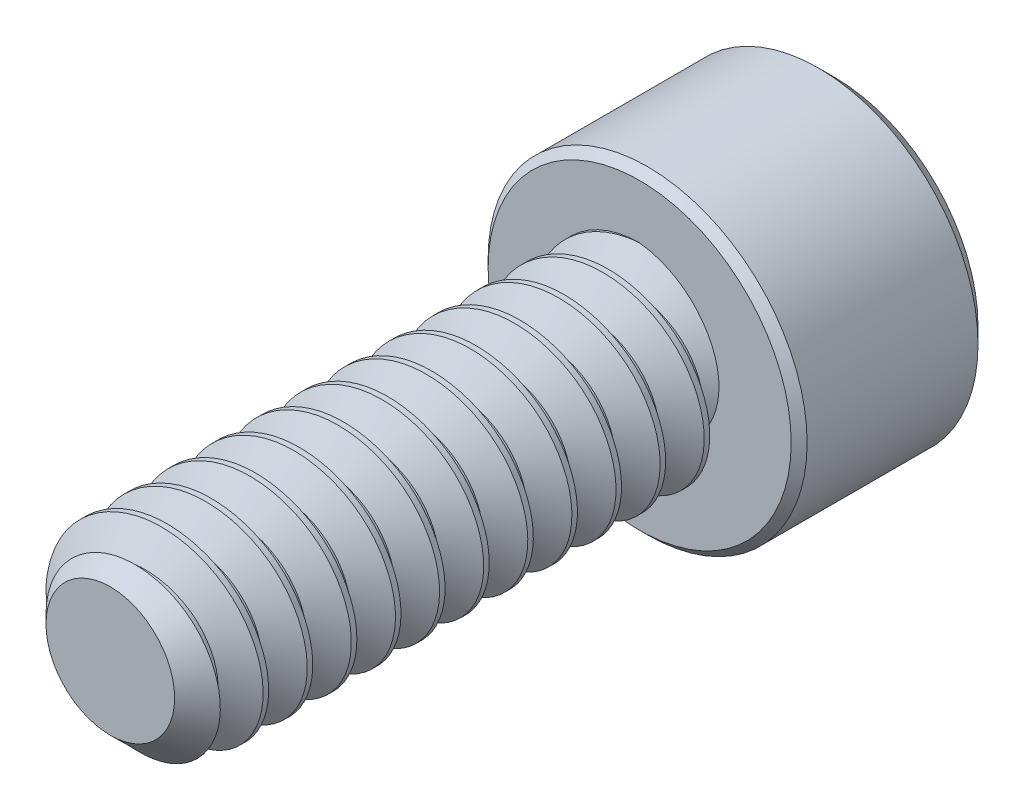
SolidWorks part; units mm, degrees
ref_plane "Front Plane" through (0, 0, 0) normal (0, 0, 1) x (1, 0, 0)
ref_plane "Top Plane" through (0, 0, 0) normal (0, 1, 0) x (1, 0, 0)
ref_plane "Right Plane" through (0, 0, 0) normal (1, 0, 0) x (0, 0, -1)
sketch "Sketch0" plane through (0, 0, 0) normal (1, 0, 0) x (0, 0, -1)
  line L0 (0, 0) -> (9.525, 0) construction
  point P2 (13.0302, 0)
  point P4 (0, 0)
  dimension "D1" = 9.525
  dimension "D2" = 3.5052
  dimension "Min Thread" = 0
sketch "Sketch1" plane through (0, 0, 0) normal (0, 0, 1) x (1, 0, 0)
  circle A0 centre (0, 0) radius 1.7526
  dimension "OD" = 3.5052
extrude "Extrude1" add sketch "Sketch1" against normal blind 9.525
sketch "Sketch2" plane through (0, 0, 0) normal (0, 0, 1) x (1, 0, 0)
  circle A0 centre (0, 0) radius 1.7526 construction
  circle A1 centre (0, 0) radius 1.7526
curve "Helix/Spiral1" pitch 0.7937 height 10.3188 turns 13 parameters "pitch"=0.7937
chamfer "Chamfer3" distance 0.5953 angle 45 1 edges at (1.7526, 0, 0)
sketch "Sketch3" plane through (0, 0, 0) normal (1, 0, 0) x (0, 0, -1)
  line L0 (-0.6945, 1.7526) -> (-0.3969, 1.237)
  line L1 (-0.3969, 1.237) -> (-0.2977, 1.237)
  line L2 (-0.2977, 1.237) -> (0, 1.7526)
  line L3 (-0.6945, 1.7526) -> (0, 1.7526)
  line L4 (-0.3473, 1.7526) -> (-0.3473, 1.237) construction
  line L5 (-0.5457, 1.4948) -> (-0.1488, 1.4948) construction
  line L6 (0, 1.7526) -> (0, -1.7526) construction
  dimension "D1" = 0.0992
  dimension "D2" = 0.3969
  dimension "D3" = 60
sweep "Cut-Sweep1" cut profiles "Sketch3" path "Helix/Spiral1"
sketch "Sketch5" plane through (0, 0, 0) normal (1, 0, 0) x (0, 0, -1)
  line L0 (9.525, -1.2539) -> (9.525, 1.2505) construction
  line L1 (9.525, 1.7526) -> (0, 1.7526)
  line L2 (9.525, 1.7526) -> (9.525, 0)
  line L3 (9.525, 0) -> (-0.6379, 0)
  line L4 (0, 0) -> (9.525, 0) construction
  line L5 (0, 1.7526) -> (-0.6379, 0)
  line L6 (0, 0) -> (12.065, 0) construction
  dimension "D1" = 70
  dimension "D3" = 2.54
revolve "partially thread" [suppressed] add sketch "Sketch5" angle 360 about L6
sketch "Sketch6" plane through (0, 0, -9.525) normal (0, 0, -1) x (-1, 0, 0)
  circle A0 centre (0, 0) radius 2.8702
  dimension "head dia" = 5.7404
extrude "Extrude2" add sketch "Sketch6" along normal blind 3.5052
sketch "Sketch7" plane through (0, 0, -13.0302) normal (0, 0, -1) x (-1, 0, 0)
  line L1 (0, 1.604) -> (-1.3891, 0.802)
  line L2 (-1.3891, 0.802) -> (-1.3891, -0.802)
  line L3 (-1.3891, -0.802) -> (0, -1.604)
  line L4 (0, -1.604) -> (1.3891, -0.802)
  line L5 (1.3891, -0.802) -> (1.3891, 0.802)
  line L6 (1.3891, 0.802) -> (0, 1.604)
  circle A0 centre (0, 0) radius 1.3891 construction
  dimension "hex dia" = 2.7781
extrude "Cut-Extrude1" cut sketch "Sketch7" against normal blind 2.0836
sketch "Sketch8" plane through (0, 0, -13.0302) normal (0, 0, -1) x (-1, 0, 0)
  circle A0 centre (0, 0) radius 1.604
extrude "Cut-Extrude2" cut sketch "Sketch8" against normal through all draft 45
chamfer "Chamfer1" distance 0.287 angle 45 1 edges at (-2.8702, 0, -13.0302)
chamfer "Chamfer2" distance 0.1435 angle 45 1 edges at (-2.8702, 0, -9.525)
sketch "Sketch9" plane through (0, 0, 0) normal (1, 0, 0) x (0, 0, -1)
  line L0 (0, 1.7526) -> (0, -1.7526) construction
  line L1 (1.9844, 1.7526) -> (1.9844, -1.7526) construction
  line L2 (13.0302, 2.8702) -> (13.0302, -2.8702) construction
  line L3 (9.525, 2.8702) -> (9.525, -2.8702) construction
  line L4 (9.525, 2.7267) -> (9.525, -2.7267) construction
  line L5 (13.0302, -2.5832) -> (13.0302, 2.5832) construction
  line L6 (9.525, -2.8702) -> (9.525, 2.8702) construction
  line L7 (0, 1.1573) -> (0, -1.1573) construction
  line L8 (-0.6945, 1.7526) -> (0, 1.7526) construction
  line L9 (1.9844, 0) -> (0, 0) construction
  dimension "D1" = 1.9844
equation "\"D3@Helix/Spiral1\" = \"screw length@Extrude1\"+\"pitch@Helix/Spiral1\""
equation "\"D1@Sketch3\" = \"pitch@Helix/Spiral1\"*.125"
equation "\"D2@Sketch3\" = \"pitch@Helix/Spiral1\"*.5"
equation "\"D1@Cut-Extrude1\" = \"hex dia@Sketch7\"*.75"
equation "\"D1@Chamfer1\" = \"head dia@Sketch6\"*.05"
equation "\"D1@Sketch9\" = \"pitch@Helix/Spiral1\"*2.50"
equation "\"D1@Chamfer2\" = \"D1@Chamfer1\"/2"
equation "\"D1@Chamfer3\" = \"pitch@Helix/Spiral1\"*.750"
equation "\"D1@Sketch0\" = \"screw length@Extrude1\""
equation "\"D2@Sketch0\" = \"head depth@Extrude2\""
